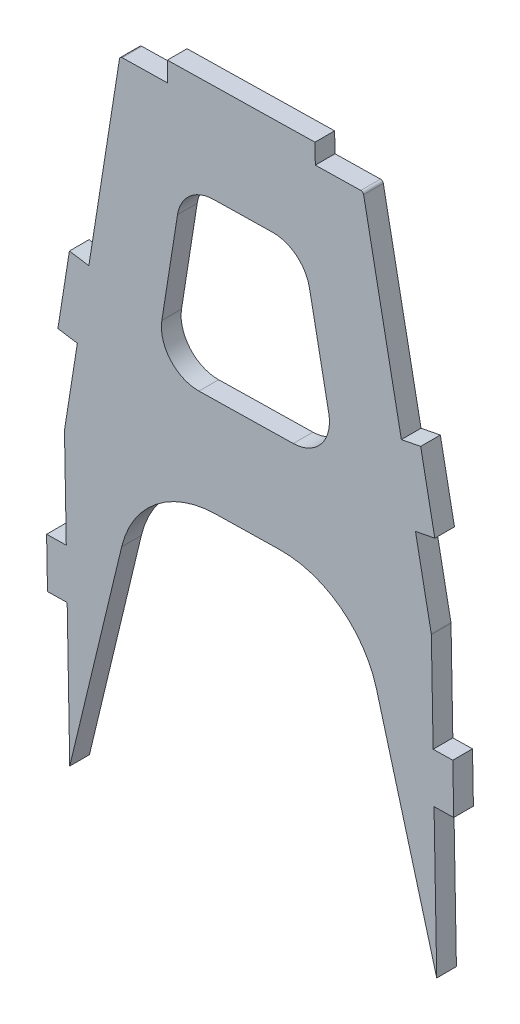
SolidWorks part; units mm, degrees
ref_plane "Front Plane" through (0, 0, 0) normal (0, 0, 1) x (1, 0, 0)
ref_plane "Top Plane" through (0, 0, 0) normal (0, 1, 0) x (1, 0, 0)
ref_plane "Right Plane" through (0, 0, 0) normal (1, 0, 0) x (0, 0, -1)
sketch "Sketch5" plane through (0, 0, -50.8) normal (0, 0, -1) x (-1, 0, 0)
  line L0 (-56.2121, -96.1075) -> (-52.1347, -75.2213) construction
  line L1 (38.4436, -97.8363) -> (35.1317, -76.8152) construction
  line L2 (40.1498, -76.0246) -> (35.1317, -76.8152) construction
  line L3 (40.1498, -76.0246) -> (37.1849, -57.2067) construction
  line L4 (37.1849, -57.2067) -> (32.1668, -57.9973) construction
  line L5 (-57.1206, -74.248) -> (-52.1347, -75.2213) construction
  line L6 (-57.1206, -74.248) -> (-53.4705, -55.5509) construction
  line L7 (-53.4705, -55.5509) -> (-48.4846, -56.5243) construction
  line L8 (-48.4846, -56.5243) -> (-38.7512, -6.6655) construction
  line L9 (-26.1883, -1.2053) -> (-26.281, -6.2844) construction
  line L10 (-38.0148, -6.0701) -> (-26.281, -6.2844) construction
  line L11 (32.1668, -57.9973) -> (24.2605, -7.8164) construction
  line L12 (23.5464, -7.1945) -> (11.8126, -6.9802) construction
  line L13 (11.9054, -1.9011) -> (11.8126, -6.9802) construction
  line L14 (-7.1414, -1.5532) -> (-26.1883, -1.2053) construction
  line L15 (-7.1414, -1.5532) -> (11.9054, -1.9011) construction
  line L16 (-56.2121, -96.1075) -> (-52.1347, -75.2213)
  line L17 (38.4436, -97.8363) -> (35.1317, -76.8152)
  line L18 (40.1498, -76.0246) -> (35.1317, -76.8152)
  line L19 (40.1498, -76.0246) -> (37.1849, -57.2067)
  line L20 (37.1849, -57.2067) -> (32.1668, -57.9973)
  line L21 (-57.1206, -74.248) -> (-52.1347, -75.2213)
  line L22 (-57.1206, -74.248) -> (-53.4705, -55.5509)
  line L23 (-53.4705, -55.5509) -> (-48.4846, -56.5243)
  line L24 (-48.4846, -56.5243) -> (-38.7512, -6.6655)
  line L25 (-26.1883, -1.2053) -> (-26.281, -6.2844)
  line L26 (-38.0148, -6.0701) -> (-26.281, -6.2844)
  line L27 (32.1668, -57.9973) -> (24.2605, -7.8164)
  line L28 (23.5464, -7.1945) -> (11.8126, -6.9802)
  line L29 (11.9054, -1.9011) -> (11.8126, -6.9802)
  line L30 (-7.1414, -1.5532) -> (-26.1883, -1.2053)
  line L31 (-7.1414, -1.5532) -> (11.9054, -1.9011)
  line L32 (-56.2121, -96.1075) -> (38.4436, -97.8363)
  line L33 (19.103, -97.4831) -> (8.035, -27.2346)
  line L34 (-23.2456, -26.6633) -> (8.035, -27.2346)
  line L35 (-23.2456, -26.6633) -> (-36.8714, -96.4607)
  line L36 (-31.9296, -71.1467) -> (15.0889, -72.0055)
  line L37 (19.103, -97.4831) -> (37.0949, -172.2945)
  line L38 (-36.8714, -96.4607) -> (-57.6148, -172.2945)
  line L39 (-56.6895, -121.6309) -> (-56.2256, -96.2351) construction
  line L40 (37.9886, -123.3602) -> (38.4525, -97.9644) construction
  line L41 (-61.5587, -388.2234) -> (-56.9214, -134.3288) construction
  line L42 (-56.9214, -134.3288) -> (-62.0005, -134.236) construction
  line L55 (-61.7686, -121.5381) -> (-62.0005, -134.236) construction
  line L56 (-56.6895, -121.6309) -> (-61.7686, -121.5381) construction
  line L57 (-56.6895, -121.6309) -> (-56.2256, -96.2351) construction
  line L58 (-61.5587, -388.2234) -> (-56.9214, -134.3288)
  line L59 (-56.9214, -134.3288) -> (-62.0005, -134.236)
  line L60 (-61.7686, -121.5381) -> (-62.0005, -134.236)
  line L61 (-56.6895, -121.6309) -> (-61.7686, -121.5381)
  line L62 (-56.6895, -121.6309) -> (-56.2256, -96.2351)
  line L63 (33.1194, -389.9527) -> (37.7567, -136.058) construction
  line L64 (43.5316, -98.0572) -> (43.0678, -123.4529) construction
  line L65 (37.7567, -136.058) -> (42.8359, -136.1508) construction
  line L66 (43.0678, -123.4529) -> (42.8359, -136.1508) construction
  line L67 (37.9886, -123.3602) -> (43.0678, -123.4529) construction
  line L68 (37.9886, -123.3602) -> (38.4525, -97.9644) construction
  line L69 (33.1194, -389.9527) -> (37.7567, -136.058)
  line L70 (43.5316, -98.0572) -> (43.0678, -123.4529)
  line L71 (37.7567, -136.058) -> (42.8359, -136.1508)
  line L72 (43.0678, -123.4529) -> (42.8359, -136.1508)
  line L73 (37.9886, -123.3602) -> (43.0678, -123.4529)
  line L74 (37.9886, -123.3602) -> (38.4525, -97.9644)
  arc A0 (-38.0148, -6.0701) -> (-38.7512, -6.6655) centre (-38.0282, -6.8066) ccw construction
  arc A1 (24.2605, -7.8164) -> (23.5464, -7.1945) centre (23.5329, -7.931) ccw construction
  arc A2 (-38.0148, -6.0701) -> (-38.7512, -6.6655) centre (-38.0282, -6.8066) ccw
  arc A3 (24.2605, -7.8164) -> (23.5464, -7.1945) centre (23.5329, -7.931) ccw
  arc A8 (-56.2121, -96.1075) -> (-56.2256, -96.2351) centre (-55.4891, -96.2486) ccw construction
  arc A9 (-56.2121, -96.1075) -> (-56.2256, -96.2351) centre (-55.4891, -96.2486) ccw
  arc A10 (38.4525, -97.9644) -> (38.4436, -97.8363) centre (37.716, -97.9509) ccw construction
  arc A11 (38.4525, -97.9644) -> (38.4436, -97.8363) centre (37.716, -97.9509) ccw
  point P36 (-61.5211, -149.8576)
  point P38 (-62.466, -196.3749)
  point P41 (-61.7881, -215.7065)
  point P45 (0, 0)
  point P48 (0, 0)
  point P50 (40.9683, -201.7487)
  point P52 (46.9531, -164.9562)
  point P53 (-61.8707, -163.7821)
  point P54 (-61.9019, -146.4369)
  point P55 (0, 0)
  point P56 (0, 0)
  point P57 (-66.6348, -165.4869)
  point P58 (-61.9019, -165.4869)
  point P59 (0, 0)
  point P60 (-61.9019, -165.4869)
  point P61 (-61.9403, -167.5927)
  point P62 (-61.9852, -170.0492)
  point P63 (-66.2798, -146.0526)
  point P64 (-66.9499, -163.688)
  point P66 (41.7098, -196.9665)
  dimension "D1" = 19.05
  dimension "D2" = 19.05
  dimension "D3" = 25.4
  dimension "D4" = 25.4
  dimension "D5" = 76.2
extrude "Boss-Extrude2" add sketch "Sketch5" along normal blind 5.08 contours L35 L36 L33 L34 | L32 L37 | L32 L38 | L30 L25 L26 A2 L24 L23 L22 L21 L16 L32 L17 L18 L19 L20 L27 A3 L28 L29 L31 region at (50.9693, -122.1287, -50.8) region at (-32.279, -123.1311, -50.8) region at (8.0401, -50.7575, -50.8)
fillet "Fillet2" radius 9.525 4 edges at (23.2456, -26.6633, -53.34) (-8.035, -27.2346, -53.34) (31.9296, -71.1467, -53.34) (-15.0889, -72.0055, -53.34)
fillet "Fillet3" radius 25.4 2 edges at (-19.103, -97.4831, -53.34) (36.8714, -96.4607, -53.34)
